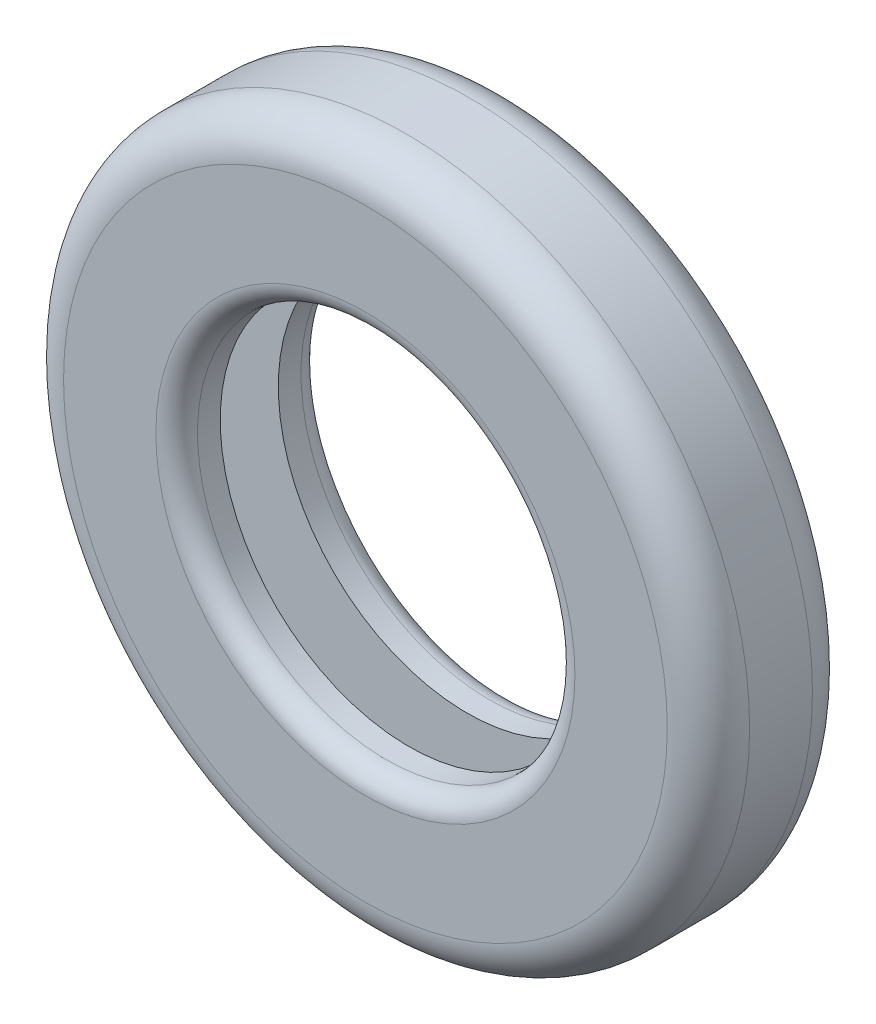
SolidWorks part; units mm, degrees
ref_plane "Front Plane" through (0, 0, 0) normal (0, 0, 1) x (1, 0, 0)
ref_plane "Top Plane" through (0, 0, 0) normal (0, 1, 0) x (1, 0, 0)
ref_plane "Right Plane" through (0, 0, 0) normal (1, 0, 0) x (0, 0, -1)
sketch "Sketch1" plane through (0, 0, 0) normal (0, 0, 1) x (1, 0, 0)
  circle A0 centre (0, 0) radius 165.1
  dimension "D1" = 330.2
extrude "Extrude-Thin1" add sketch "Sketch1" along normal blind 127 thin thin type one direction wall 135
fillet "Fillet2" radius 36.02 2 edges at (300.1, 0, 127) (300.1, 0, 0)
fillet "Fillet3" radius 18.24 2 edges at (165.1, 0, 127) (165.1, 0, 0)
shell "Shell3" thickness 38.1 removed face at (165.1, 0, 108.76)
